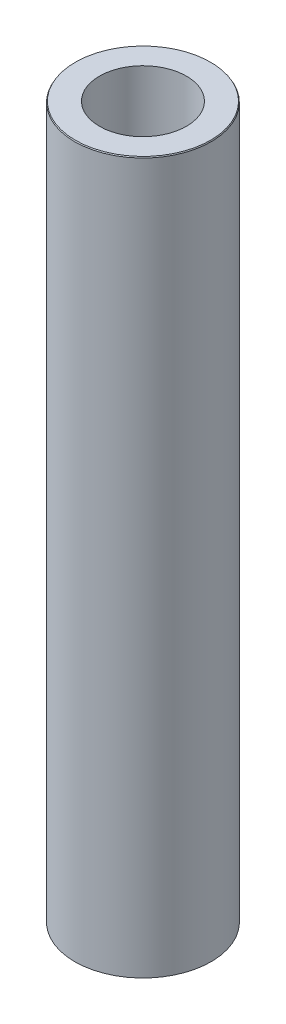
SolidWorks part; units mm, degrees
ref_plane "Front Plane" through (0, 0, 0) normal (0, 0, 1) x (1, 0, 0)
ref_plane "Top Plane" through (0, 0, 0) normal (0, 1, 0) x (1, 0, 0)
ref_plane "Right Plane" through (0, 0, 0) normal (1, 0, 0) x (0, 0, -1)
sketch "Sketch1" plane through (0, 0, 0) normal (0, 1, 0) x (1, 0, 0)
  circle A0 centre (0, 0) radius 57.5
  dimension "SHAFT_OD" = 115
extrude "Boss-Extrude1" add sketch "Sketch1" along normal blind 600
sketch "Sketch2" plane through (0, 0, 0) normal (0, 1, 0) x (1, 0, 0)
  circle A0 centre (0, 0) radius 36.671
  dimension "BORE_D" = 73.3421
extrude "Cut-Extrude1" cut sketch "Sketch2" along normal through all
chamfer "Chamfer1" distance 0.8586 angle 30 2 edges at (0, 600, 57.5) (0, 0, 57.5) first distance on face at (0, 600, 57.5) first distance on face at (0, 0, 36.671)
